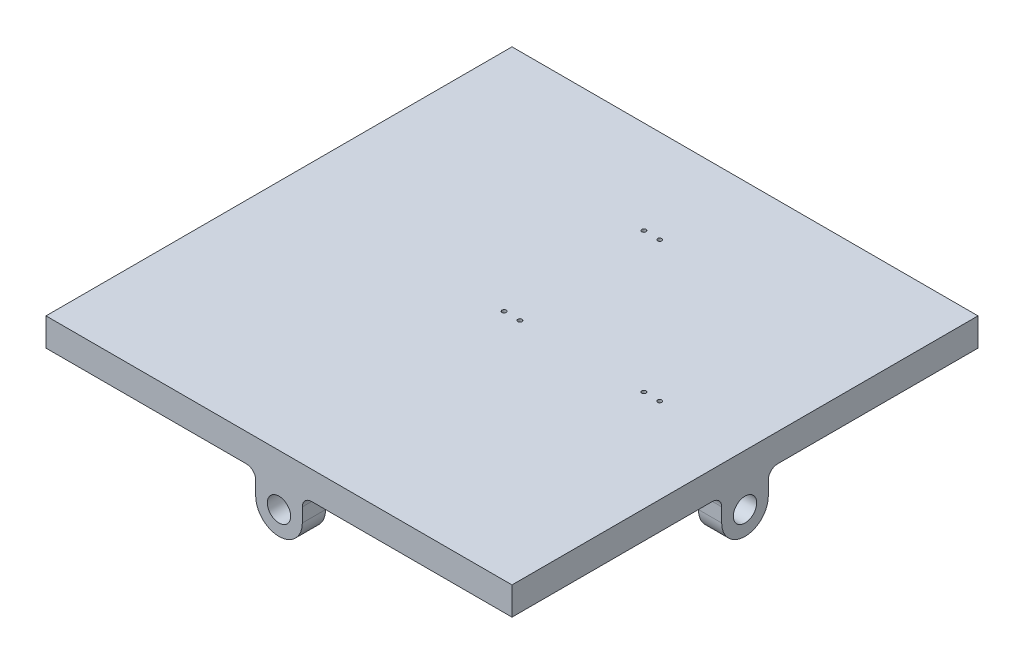
SolidWorks part; units mm, degrees
ref_plane "Plano frontal" through (0, 0, 0) normal (0, 0, 1) x (1, 0, 0)
ref_plane "Plano superior" through (0, 0, 0) normal (0, 1, 0) x (1, 0, 0)
ref_plane "Plano direito" through (0, 0, 0) normal (1, 0, 0) x (0, 0, -1)
sketch "Esboço1" plane through (0, 0, 0) normal (0, 1, 0) x (1, 0, 0)
  line L1 (0, 0) -> (500, 0)
  line L2 (0, 0) -> (0, 500)
  line L3 (0, 500) -> (500, 500)
  line L4 (500, 0) -> (500, 500)
  dimension "D1" = 500
extrude "Ressalto-extrusão1" add sketch "Esboço1" along normal blind 30
sketch "Esboço2" plane through (0, 0, 0) normal (0, -1, 0) x (1, 0, 0)
  line L0 (0, -500) -> (0, 0) construction
  line L1 (225, -25) -> (275, -25)
  line L2 (225, -25) -> (225, 0)
  line L3 (225, 0) -> (275, 0)
  line L4 (275, -25) -> (275, 0)
  line L5 (0, 0) -> (500, 0) construction
  line L6 (500, 0) -> (500, -500) construction
  line L7 (475, -225) -> (500, -225)
  line L9 (500, -500) -> (0, -500) construction
  line L14 (475, -225) -> (475, -275)
  line L15 (475, -275) -> (500, -275)
  line L16 (500, -225) -> (500, -275)
  line L22 (0, -225) -> (0, -275)
  line L23 (25, -275) -> (0, -275)
  line L24 (25, -225) -> (25, -275)
  line L25 (25, -225) -> (0, -225)
  line L26 (275, -475) -> (275, -500)
  line L27 (225, -500) -> (275, -500)
  line L28 (225, -475) -> (225, -500)
  line L29 (225, -475) -> (275, -475)
  point P6 (250, 0)
  point P21 (500, -250)
  dimension "D1" = 250
  dimension "D2" = 50
  dimension "D3" = 25
  dimension "D4" = 0
  dimension "D5" = 250
  dimension "D6" = 50
  dimension "D7" = 25
  dimension "D8" = 0
extrude "Ressalto-extrusão2" add sketch "Esboço2" along normal blind 50
sketch "Esboço3" plane through (0, 0, 0) normal (-1, 0, 0) x (0, 0, 1)
  line L3 (-225, -50) -> (-275, -50) construction
  line L4 (-275, -50) -> (-275, 0) construction
  circle A0 centre (-250, -25) radius 12.5
  dimension "D3" = 25
  dimension "D1" = 25
  dimension "D2" = 25
extrude "Corte-extrusão1" cut sketch "Esboço3" against normal through all
sketch "Esboço4" plane through (0, 0, 0) normal (0, 0, 1) x (1, 0, 0)
  line L0 (275, -50) -> (275, 0) construction
  line L1 (0, 0) -> (225, 0) construction
  circle A0 centre (250, -25) radius 12.5
  dimension "D3" = 25
  dimension "D1" = 25
  dimension "D2" = 25
extrude "Corte-extrusão2" cut sketch "Esboço4" against normal through all
fillet "Filete1" radius 25 8 edges at (275, -50, -487.5) (225, -50, -487.5) (12.5, -50, -275) (12.5, -50, -225) (487.5, -50, -275) (487.5, -50, -225) (275, -50, -12.5) (225, -50, -12.5)
fillet "Filete4" radius 10 8 edges at (487.5, 0, -275) (487.5, 0, -225) (275, 0, -12.5) (225, 0, -12.5) (12.5, 0, -225) (275, 0, -487.5) (225, 0, -487.5) (12.5, 0, -275)
sketch "Esboço5" plane through (0, 0, 0) normal (0, -1, 0) x (1, 0, 0)
  line L0 (25, -285) -> (25, -215) construction
  line L1 (50, -25) -> (450, -25)
  line L2 (25, -50) -> (25, -450)
  line L3 (50, -475) -> (450, -475)
  line L4 (475, -50) -> (475, -450)
  line L6 (215, -25) -> (285, -25) construction
  line L7 (475, -215) -> (475, -285) construction
  line L8 (285, -475) -> (215, -475) construction
  line L9 (25, -450) -> (50, -475)
  line L10 (450, -475) -> (475, -450)
  line L11 (25, -50) -> (50, -25)
  line L12 (450, -25) -> (475, -50)
  point P0 (25, -25)
  point P1 (475, -475)
  point P2 (25, -475)
  point P3 (475, -25)
extrude "Corte-extrusão3" cut sketch "Esboço5" against normal blind 15
sketch "Esboço6" plane through (0, 15, 0) normal (0, -1, 0) x (1, 0, 0)
  line L0 (25, -250) -> (475, -250) construction
  line L1 (25, -50) -> (25, -450) construction
  line L2 (475, -450) -> (475, -50) construction
  line L3 (250, -25) -> (250, -475) construction
  line L4 (450, -25) -> (50, -25) construction
  line L5 (50, -475) -> (450, -475) construction
  circle A0 centre (241.5, -250) radius 2.25
  circle A1 centre (258.5, -250) radius 2.25
  circle A2 centre (391.5, -250) radius 2.25
  circle A3 centre (408.5, -250) radius 2.25
  circle A6 centre (241.5, -400) radius 2.25
  circle A7 centre (258.5, -400) radius 2.25
  circle A8 centre (391.5, -400) radius 2.25 [skipped]
  circle A9 centre (408.5, -400) radius 2.25 [skipped]
  dimension "D2" = 4.5
  dimension "D3" = 4.5
  dimension "D1" = 17
  dimension "D4" = 8.5
  dimension "D5" = 2
  dimension "D6" = 2
extrude "Corte-extrusão4" cut sketch "Esboço6" against normal through all
